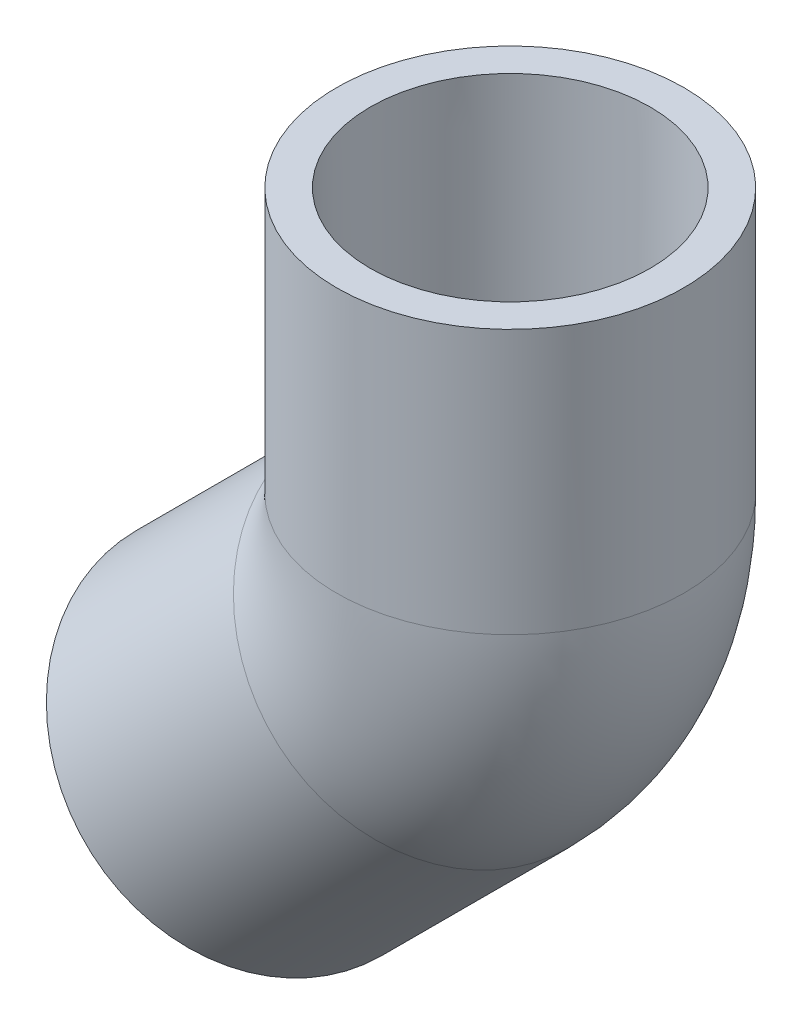
SolidWorks part; units mm, degrees
ref_plane "Front Plane" through (0, 0, 0) normal (0, 0, 1) x (1, 0, 0)
ref_plane "Top Plane" through (0, 0, 0) normal (0, 1, 0) x (1, 0, 0)
ref_plane "Right Plane" through (0, 0, 0) normal (1, 0, 0) x (0, 0, -1)
sketch "Sketch0" plane through (0, 0, 0) normal (0, 0, 1) x (1, 0, 0)
  line L0 (-24.1344, -24.1344) -> (0, 0) construction
  line L1 (0, 0) -> (0, 34.1313) construction
  line L2 (-6.1739, -6.1739) -> (0, 0) construction
  line L3 (0, 0) -> (0, 8.7312) construction
  line L4 (-35.921, -12.3479) -> (-12.3479, -35.921) construction
  line L5 (-15.5673, 3.2194) -> (-33.6355, -14.6333) construction
  line L6 (-15.5673, 3.2194) -> (3.2194, -15.5673) construction
  line L7 (3.2194, -15.5673) -> (-14.6333, -33.6355) construction
  line L8 (-33.6355, -14.6333) -> (-14.6333, -33.6355) construction
  line L9 (-16.6687, 34.1313) -> (16.6687, 34.1313) construction
  line L10 (-13.4366, 34.1313) -> (13.4366, 34.1313) construction
  line L11 (13.4366, 34.1313) -> (13.2842, 8.7312) construction
  line L12 (13.2842, 8.7312) -> (-13.2842, 8.7312) construction
  line L13 (-13.2842, 8.7312) -> (-13.4366, 34.1313) construction
  line L14 (-13.5737, 1.2258) -> (1.2258, -13.5737) construction
  line L18 (-10.4648, 8.7312) -> (10.4648, 8.7312) construction
  dimension "D1" = 45
  dimension "H" = 34.1313
  dimension "J" = 8.7312
  dimension "M" = 33.3375
  dimension "OD A" = 26.8732
  dimension "OD B" = 26.5684
  dimension "ID" = 20.9296
sketch "Sketch1" plane through (0, 0, 0) normal (0, 0, 1) x (1, 0, 0)
  line L0 (-24.1344, -24.1344) -> (0, 0) construction
  line L1 (-24.1344, -24.1344) -> (0, 0) construction
  line L3 (-12.3479, -35.921) -> (5.6127, -17.9605)
  line L4 (-12.3479, -35.921) -> (-14.6333, -33.6355)
  line L5 (-14.6333, -33.6355) -> (3.2194, -15.5673)
  line L6 (5.6127, -17.9605) -> (3.2194, -15.5673)
revolve "Revolve1" add sketch "Sketch1" angle 360 about L1
sketch "Sketch2" plane through (0, 0, 0) normal (0, 0, 1) x (1, 0, 0)
  line L0 (13.4366, 34.1313) -> (13.2842, 8.7312)
  line L1 (13.2842, 8.7312) -> (16.6687, 8.7312)
  line L2 (16.6687, 8.7312) -> (16.6687, 34.1313)
  line L3 (16.6687, 34.1313) -> (13.4366, 34.1313)
  line L4 (0, 0) -> (0, 34.1313) construction
  line L5 (0, 0) -> (0, 34.1313) construction
revolve "Revolve2" add sketch "Sketch2" angle 360 about L5
sketch "Sketch3" plane through (-6.1739, -6.1739, 0) normal (0.7071, 0.7071, 0) x (0, 0, -1)
  circle A0 centre (0, 0) radius 10.4648
  circle A1 centre (0, 0) radius 16.6687
sketch "Sketch4" plane through (0, 0, 0) normal (0, 0, 1) x (1, 0, 0)
  line L0 (-24.1344, -24.1344) -> (0, 0) construction
  line L1 (0, 0) -> (0, 34.1313) construction
  line L2 (-24.1344, -24.1344) -> (-6.1739, -6.1739) construction
  line L3 (0, 8.7313) -> (0, 34.1313) construction
  arc A0 (-6.1739, -6.1739) -> (0, 8.7313) centre (-21.0791, 8.7313) ccw
sweep "Sweep1" add profiles "Sketch3" path "Sketch4"
